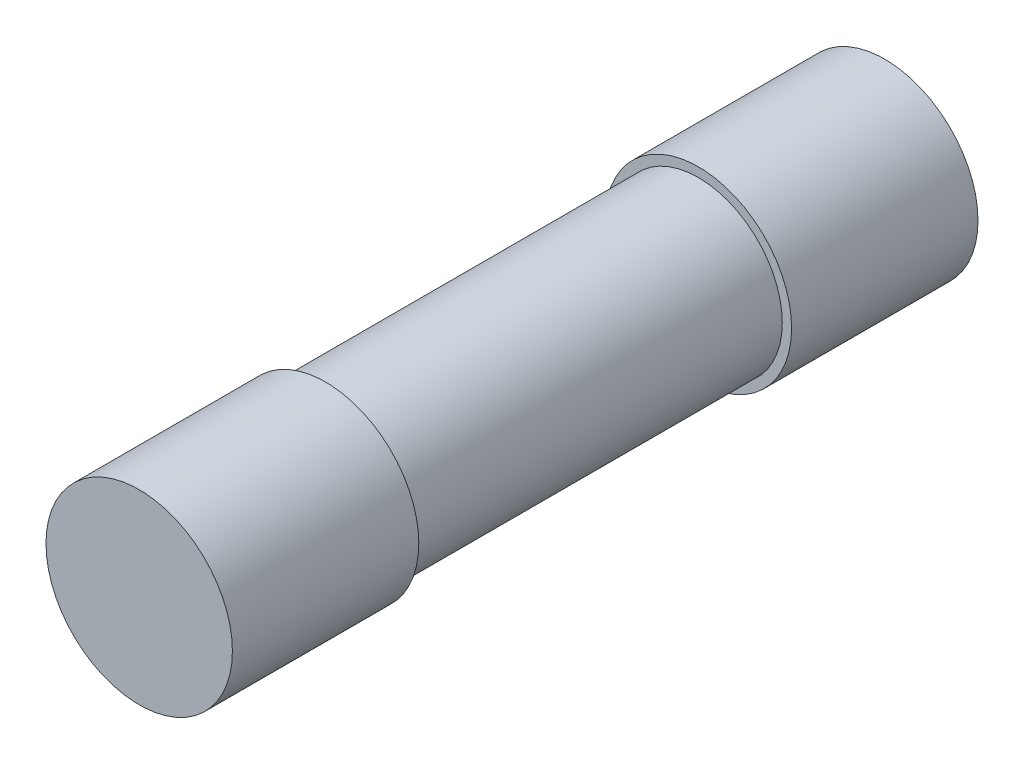
SolidWorks part; units mm, degrees
ref_plane "Спереди" through (0, 0, 0) normal (0, 0, 1) x (1, 0, 0)
ref_plane "Сверху" through (0, 0, 0) normal (0, 1, 0) x (1, 0, 0)
ref_plane "Справа" through (0, 0, 0) normal (1, 0, 0) x (0, 0, -1)
sketch "Эскиз1" plane through (0, 0, 0) normal (0, 0, 1) x (1, 0, 0)
  circle A0 centre (0, 0) radius 2.5
  dimension "D1" = 5
extrude "Бобышка-Вытянуть1" add sketch "Эскиз1" against normal blind 5 from offset 10
sketch "Эскиз2" plane through (0, 0, 0) normal (0, 0, 1) x (1, 0, 0)
  circle A0 centre (0, 0) radius 2.25
  dimension "D1" = 4.5
extrude "Бобышка-Вытянуть2" add sketch "Эскиз2" along normal blind 6 and the other way blind 6
mirror "Зеркальное отражение1" about plane through (0, 0, 0) normal (0, 0, 1) of "Бобышка-Вытянуть1"
